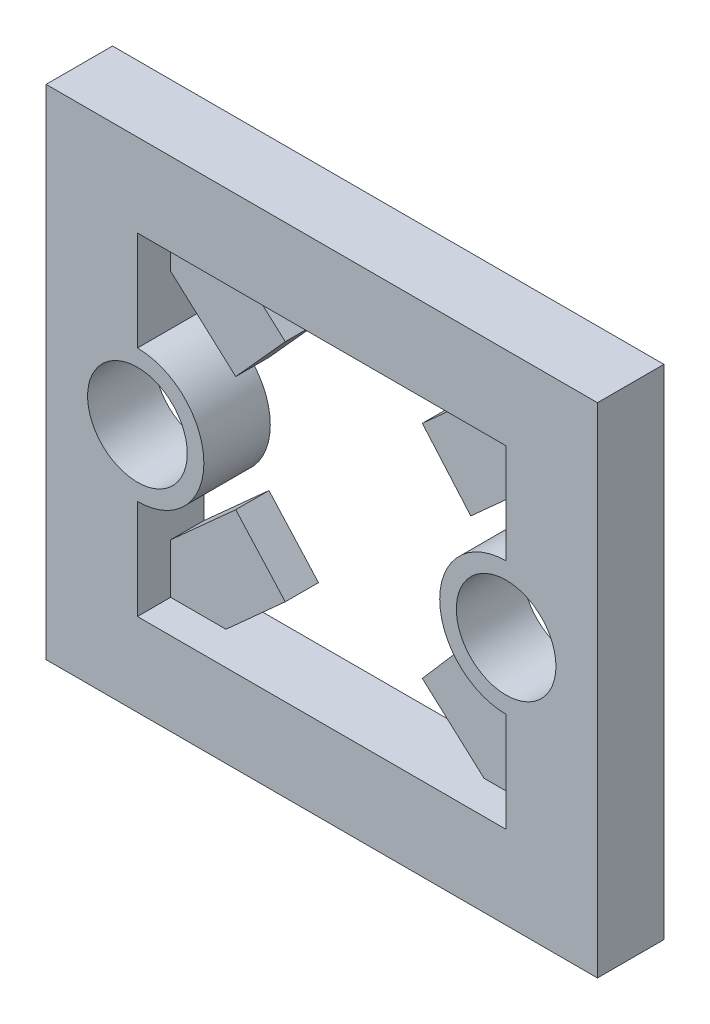
SolidWorks part; units mm, degrees
material "ABS"
ref_plane "Front Plane" through (0, 0, 0) normal (0, 0, 1) x (1, 0, 0)
ref_plane "Top Plane" through (0, 0, 0) normal (0, 1, 0) x (1, 0, 0)
ref_plane "Right Plane" through (0, 0, 0) normal (1, 0, 0) x (0, 0, -1)
sketch "Sketch1" plane through (0, 0, 0) normal (0, 0, 1) x (1, 0, 0)
  line L0 (12.065, 30.099) -> (12.065, 36.2935) construction
  line L1 (0, 0) -> (24.13, 0) construction
  line L2 (0, 0) -> (0, 30.099) construction
  line L3 (0, 30.099) -> (24.13, 30.099) construction
  line L4 (24.13, 0) -> (24.13, 30.099) construction
  line L5 (-6.1945, -6.1945) -> (30.3245, -6.1945)
  line L6 (-6.1945, -6.1945) -> (-6.1945, 36.2935)
  line L7 (-6.1945, 36.2935) -> (30.3245, 36.2935)
  line L8 (30.3245, -6.1945) -> (30.3245, 36.2935)
  line L9 (12.065, -6.1945) -> (12.065, 0) construction
  line L10 (-6.1945, 15.0495) -> (0, 15.0495) construction
  line L11 (30.3245, 15.0495) -> (24.13, 15.0495) construction
  line L12 (0, 0) -> (-6.1945, 0) construction
  line L13 (0, 0) -> (0, -6.1945) construction
  line L14 (-6.1945, -6.1945) -> (-4.5052, -4.5052) construction
  line L15 (-1.5, 15.0495) -> (0, 15.0495) construction
  line L16 (-2.3839, -2.3839) -> (-4.5052, -4.5052) construction
  line L17 (-4.9445, -3.4445) -> (-6.1945, -3.4445) construction
  line L18 (-1.5, -1.5) -> (25.63, -1.5)
  line L19 (-1.5, -1.5) -> (-1.5, 31.599)
  line L20 (-1.5, 31.599) -> (25.63, 31.599)
  line L21 (25.63, -1.5) -> (25.63, 31.599)
  line L22 (25.63, 15.0495) -> (24.13, 15.0495) construction
  line L23 (12.065, 31.599) -> (12.065, 30.099) construction
  line L24 (12.065, -1.5) -> (12.065, 0) construction
  line L25 (-2.3839, -2.3839) -> (-1.5, -1.5)
  line L26 (4.908, 13.095) -> (4.158, 13.095) construction
  line L27 (11.1079, 11.8549) -> (13.6479, 11.8549) construction
  line L28 (11.1079, 11.8549) -> (11.1079, 14.3949) construction
  line L29 (11.1079, 14.3949) -> (13.6479, 14.3949) construction
  line L30 (13.6479, 11.8549) -> (13.6479, 14.3949) construction
  line L31 (4.158, 20.595) -> (20.7581, 20.595)
  line L32 (4.158, 20.595) -> (4.158, 5.595)
  line L33 (4.158, 5.595) -> (20.7581, 5.595)
  line L34 (20.7581, 20.595) -> (20.7581, 5.595)
  line L35 (20.0081, 13.095) -> (20.7581, 13.095) construction
  line L36 (11.1079, 14.3949) -> (13.6479, 11.8549) construction
  line L37 (11.1079, 10.8549) -> (11.1079, 5.595) construction
  line L38 (13.6479, 14.3949) -> (11.1079, 11.8549) construction
  line L39 (13.6479, 11.8549) -> (14.355, 11.1478)
  line L40 (14.355, 11.1478) -> (14.7086, 10.7943)
  line L41 (6.908, 15.095) -> (6.908, 18.095)
  line L42 (6.908, 18.095) -> (18.0081, 18.095)
  line L43 (18.0081, 18.095) -> (18.0081, 15.095)
  line L44 (6.908, 11.095) -> (6.908, 8.095)
  line L45 (18.0081, 11.095) -> (18.0081, 8.095)
  line L46 (18.0081, 8.095) -> (6.908, 8.095)
  line L47 (6.908, 18.095) -> (18.0081, 8.095) construction
  line L48 (18.0081, 18.095) -> (6.908, 8.095) construction
  line L49 (6.908, 8.095) -> (6.7678, 8.1689)
  line L50 (8.867, 14.8302) -> (10.3588, 16.4861)
  line L51 (10.3588, 16.4861) -> (8.573, 18.095)
  line L52 (8.867, 14.8302) -> (6.908, 16.595)
  line L53 (12.4581, 18.095) -> (12.4581, 8.095) construction
  line L54 (16.0081, 13.095) -> (8.908, 13.095) construction
  line L55 (14.4851, 16.4211) -> (15.9434, 14.7349)
  line L56 (15.9434, 14.7349) -> (18.0081, 16.595)
  line L57 (14.4851, 16.4211) -> (16.3431, 18.095)
  line L58 (8.867, 11.3598) -> (6.908, 9.595)
  line L59 (10.3588, 9.7038) -> (8.573, 8.095)
  line L60 (8.867, 11.3598) -> (10.3588, 9.7038)
  line L61 (14.4851, 9.7688) -> (16.3431, 8.095)
  line L62 (14.4851, 9.7688) -> (15.9434, 11.455)
  line L63 (15.9434, 11.455) -> (18.0081, 9.595)
  circle A0 centre (3.048, 2.921) radius 1.5
  circle A1 centre (21.336, 2.921) radius 1.5
  circle A2 centre (3.048, 27.051) radius 1.5
  circle A3 centre (6.908, 13.095) radius 1.5
  circle A4 centre (18.0081, 13.095) radius 1.5
  circle A5 centre (-3.4445, -3.4445) radius 1.5
  circle A6 centre (27.5745, -3.4445) radius 1.5
  circle A7 centre (-3.4445, 33.5435) radius 1.5
  circle A8 centre (27.5745, 33.5435) radius 1.5
  circle A9 centre (3.048, 2.921) radius 2
  circle A10 centre (6.908, 13.095) radius 2
  circle A11 centre (18.0081, 13.095) radius 2
  circle A12 centre (21.336, 2.921) radius 2
  circle A13 centre (3.048, 27.051) radius 2
  circle A14 centre (11.1079, 14.3949) radius 1 construction
  circle A15 centre (13.6479, 14.3949) radius 1 construction
  circle A16 centre (11.1079, 11.8549) radius 1 construction
  circle A17 centre (13.6479, 11.8549) radius 1 construction
  circle A18 centre (12.3779, 13.1249) radius 3.2961 construction
  circle A19 centre (12.3779, 13.1249) radius 3.75 construction
  circle A20 centre (12.3779, 13.1249) radius 2.25 construction
  point P86 (9.6129, 15.6582)
  point P93 (9.6129, 15.6582)
  point P97 (15.2143, 15.578)
  point P100 (15.2143, 15.578)
  dimension "D5" = 3
  dimension "D10" = 3
  dimension "D13" = 3
  dimension "D16" = 3
  dimension "D17" = 3
  dimension "D20" = 4
  dimension "D25" = 2
  dimension "D27" = 0.5
  dimension "D28" = 15
  dimension "D29" = 4.5
  dimension "D31" = 7.5
  dimension "D1" = 24.13
  dimension "D2" = 30.099
  dimension "D3" = 3.048
  dimension "D4" = 2.921
  dimension "D6" = 21.336
  dimension "D7" = 2.921
  dimension "D8" = 3.048
  dimension "D9" = 27.051
  dimension "D11" = 13.095
  dimension "D12" = 6.908
  dimension "D14" = 18.0081
  dimension "D15" = 13.095
  dimension "D18" = 1.25
  dimension "D19" = 1.5
  dimension "D21" = 11.1079
  dimension "D22" = 11.8549
  dimension "D23" = 13.6479
  dimension "D24" = 14.3949
  dimension "D26" = 0.75
  dimension "D30" = 10
extrude "Boss-Extrude1" add sketch "Sketch1" along normal blind 2 contours A10 A3 | A11 A4 | L34 L31 L32 L33 A11 L45 L46 L44 A10 L41 L42 L43 region at (12.4581, 20.3712, 0) region at (8.2823, 14.4692, 0) region at (19.3823, 14.4692, 0)
extrude "Boss-Extrude2" add sketch "Sketch1<25>" along normal blind 1 contours L52 L50 L51 L42 L41 | L57 L55 L56 L43 L42 | L63 L62 L61 L46 L45 | L60 L58 L44 L46 L59 region at (8.446, 16.6905, 0) region at (8.446, 9.4995, 0) region at (16.4265, 16.6484, 0) region at (16.4265, 9.5415, 0)
sketch "Sketch1<25>" plane through (0, 0, 0) normal (0, 0, 1) x (1, 0, 0) same geometry as "Sketch1"
